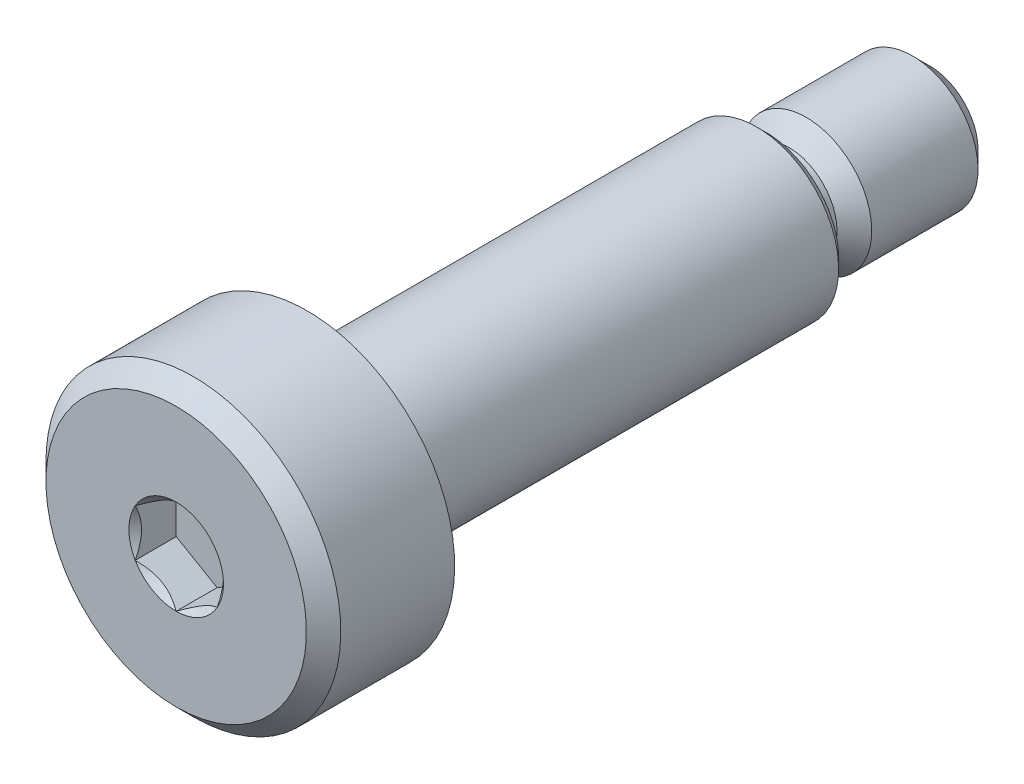
SolidWorks part; units mm, degrees
ref_plane "Front Plane" through (0, 0, 0) normal (0, 0, 1) x (1, 0, 0)
ref_plane "Top Plane" through (0, 0, 0) normal (0, 1, 0) x (1, 0, 0)
ref_plane "Right Plane" through (0, 0, 0) normal (1, 0, 0) x (0, 0, -1)
sketch "Sketch1" plane through (0, 0, 0) normal (1, 0, 0) x (0, 0, -1)
  line L0 (-11.5, 0) -> (11.5, 0) construction
  line L1 (-11.5, -4.5) -> (-11.5, 4.5)
  line L2 (-7.5, -4.5) -> (-7.5, 4.5)
  line L3 (6.5, 2.5) -> (6.5, -2.5)
  line L4 (-11.5, 1.25) -> (-11.5, -1.25)
  line L5 (11.5, 2) -> (11.5, -2)
  line L6 (11.4562, 2.0758) -> (12.1562, 2.0758) construction
  line L7 (12.1562, 2.0758) -> (11.8062, 1.4696) construction
  line L8 (11.8062, 1.4696) -> (11.4562, 2.0758) construction
  line L9 (11.8062, 2.0758) -> (11.8062, 2) construction
  line L10 (11.8062, 1.4696) -> (11.8062, 1.5453) construction
  line L11 (11.5, 2) -> (12.1125, 2) construction
  line L12 (11.4781, 2.0379) -> (12.1344, 2.0379) construction
  line L13 (11.7625, 1.5453) -> (11.85, 1.5453) construction
  line L14 (-7.5, 0) -> (-6.1, 0) construction
  line L15 (-6.1, 0) -> (5.1, 0) construction
  line L16 (5.1, 0) -> (6.5, 0) construction
  point P0 (9.05, -2)
  point P4 (0, 0)
  point P8 (-11.5, 0)
  point P11 (-7.5, 0)
  point P14 (6.5, 0)
  point P17 (-11.5, 0)
  point P20 (11.5, 0)
  point P28 (11.8062, 2)
  point P32 (11.8062, 2.0379)
  point P35 (11.8062, 1.5453)
  dimension "D1" = 2.45
  dimension "D3" = 0.0875
  dimension "D2" = 11.2
sketch "Sketch2" plane through (0, 0, 0) normal (1, 0, 0) x (0, 0, -1)
  line L0 (11.5, 0) -> (11.5, 1.475)
  line L1 (11.5, 2) -> (11.5, -2) construction
  line L2 (11.5, 1.475) -> (10.975, 2)
  line L3 (10.975, 2) -> (7.7304, 2)
  line L4 (7.7304, 2) -> (7.2, 1.4696)
  line L5 (7.2, 1.4696) -> (6.85, 1.4696)
  line L6 (6.85, 1.4696) -> (6.5, 1.4696) construction
  line L7 (6.5, 1.8196) -> (6.5, 2.22)
  line L8 (6.22, 2.5) -> (-6.6653, 2.5)
  line L9 (-6.6653, 2.5) -> (-6.8, 2.2667)
  line L10 (-6.8, 2.2667) -> (-7.2667, 2.2667)
  line L11 (-7.5, -4.5) -> (-7.5, 4.5) construction
  line L13 (-7.5, 4.5) -> (-10.975, 4.5)
  line L14 (-11.5, 3.975) -> (-11.5, 0)
  line L15 (-11.5, 0) -> (11.5, 0)
  line L16 (-10.975, 4.5) -> (-11.5, 3.975)
  line L17 (-7.5, 4.5) -> (-7.5, 2.5)
  line L18 (6.22, 2.5) -> (6.5, 2.22)
  line L19 (6.5, 2.5) -> (6.5, -2.5) construction
  arc A0 (6.85, 1.4696) -> (6.5, 1.8196) centre (6.85, 1.8196) cw
  arc A1 (-7.2667, 2.2667) -> (-7.5, 2.5) centre (-7.2667, 2.5) cw
  dimension "D1" = 45
  dimension "D2" = 0.525
  dimension "D3" = 45
  dimension "D4" = 0.35
  dimension "D5" = 0.7
  dimension "D6" = 60
  dimension "D7" = 0.2333
  dimension "D8" = 0.525
  dimension "D9" = 45
  dimension "D10" = 45
  dimension "D11" = 0.28
revolve "Revolve1" add sketch "Sketch2" angle 360 about L15
sketch "Sketch3" plane through (0, 0, 11.5) normal (0, 0, 1) x (1, 0, 0)
  line L1 (0, 1.4434) -> (-1.25, 0.7217)
  line L2 (-1.25, 0.7217) -> (-1.25, -0.7217)
  line L3 (-1.25, -0.7217) -> (0, -1.4434)
  line L4 (0, -1.4434) -> (1.25, -0.7217)
  line L5 (1.25, -0.7217) -> (1.25, 0.7217)
  line L6 (1.25, 0.7217) -> (0, 1.4434)
  circle A0 centre (0, 0) radius 1.25 construction
  circle A1 centre (0, 0) radius 4.5 construction
  circle A2 centre (0, 0) radius 4.5 construction
extrude "Cut-Extrude1" cut sketch "Sketch3" against normal blind 1.25
sketch "Sketch4" plane through (0, 0, 11.5) normal (0, 0, 1) x (1, 0, 0)
  circle A0 centre (0, 0) radius 1.4434
extrude "Cut-Extrude2" cut sketch "Sketch4" against normal blind 1.25 draft 45
ref_axis "Center Axis 1" through (0, 0, 15.6891) along (0, 0, -1)
ref_plane "Contact Plane 1" through (0, 0, 7.5) normal (0, 0, -1) x (-1, 0, 0)
sketch "Sketch6" [suppressed] plane through (0, 0, -11.5) normal (0, 0, -1) x (-1, 0, 0)
  circle A0 centre (0, 0) radius 2
curve "Helix/Spiral1" [suppressed] pitch 0.7 height 4.65 turns 6.6429
sketch "Sketch8" [suppressed] plane through (0, 0, 0) normal (1, 0, 0) x (0, 0, -1)
  line L0 (11.4781, 2.0379) -> (12.1344, 2.0379)
  line L1 (12.1344, 2.0379) -> (11.85, 1.5453)
  line L2 (11.85, 1.5453) -> (11.7625, 1.5453)
  line L3 (11.7625, 1.5453) -> (11.4781, 2.0379)
sweep "Cut-Sweep1" [suppressed] cut profiles "Sketch8" path "Helix/Spiral1"
ref_plane "Plane2" [suppressed] through (0, 0, 9.7) normal (0, 0, 1) x (1, 0, 0)
sketch "Sketch9" [suppressed] plane through (0, 0, 11.5) normal (0, 0, 1) x (1, 0, 0)
  line L0 (-0.14, 4.5) -> (0, 4.2575)
  line L1 (0, -4.5) -> (0, 4.5) construction
  line L2 (0, 4.2575) -> (0.14, 4.5)
  line L3 (0.14, 4.5) -> (-0.14, 4.5)
  line L4 (-0.14, 4.5) -> (0, 0) construction
  line L5 (0, 0) -> (0.14, 4.5) construction
  dimension "D1" = 0.28
  dimension "D2" = 3.564
extrude "Cut-Extrude3" [suppressed] cut sketch "Sketch9" against normal up to surface (1.8 mm away)
pattern_circular "CirPattern1" [suppressed] count 89 over 360 about axis through (0, 0, 11.5) along (0, 0, -1) of bodies 108
equation "\"D3@Sketch1\" = \"Thread Pitch@Sketch1\" / 8"
equation "\"D1@Sketch1\" = \"Thread Pitch@Sketch1\" * 3.5"
equation "\"D2@Sketch2\" = \"Thread Pitch@Sketch1\" * .750"
equation "\"D4@Sketch2\" = \"Thread Pitch@Sketch1\" / 2"
equation "\"D5@Sketch2\"= \"Thread Pitch@Sketch1\""
equation "\"D7@Sketch2\"=\"D5@Sketch2\"/3"
equation "\"D8@Sketch2\" = \"Thread Pitch@Sketch1\" * .750"
equation "\"D11@Sketch2\" = \"Thread Pitch@Sketch1\" * .4"
equation "\"D1@Cut-Extrude1\"=\"Drive Size@Sketch1\"/2"
equation "\"D1@Cut-Extrude2\"=\"Drive Size@Sketch1\"/2"
equation "\"D4@Helix/Spiral1\" = \"Thread Pitch@Sketch1\""
equation "\"D3@Helix/Spiral1\" = \"Thread Length@Sketch1\" - ( \"Thread Pitch@Sketch1\" / 2 )"
equation "\"D1@Plane2\"=\"Head Height@Sketch1\"*.45"
equation "\"D1@Sketch9\" = \"Thread Pitch@Sketch1\" * .4"
equation "\"D1@CirPattern1\"=(360/\"D2@Sketch9\")-12"
equation "\"D2@Sketch1\"=\"Shoulder Length@Sketch1\"*.80"
